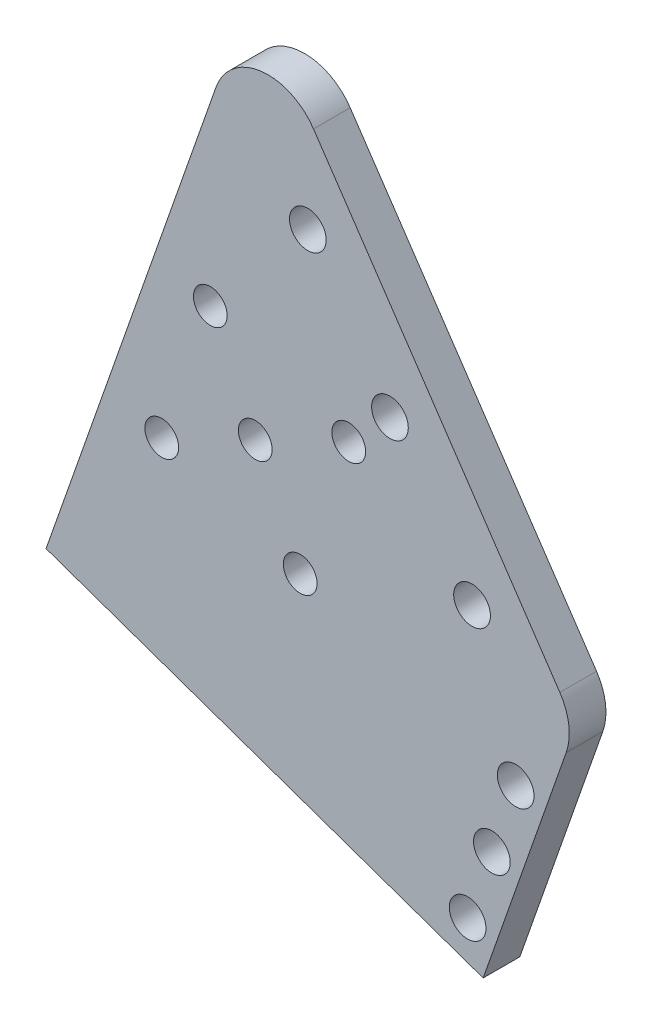
SolidWorks part; units mm, degrees
ref_plane "Front" through (0, 0, 0) normal (0, 0, 1) x (1, 0, 0)
ref_plane "Top" through (0, 0, 0) normal (0, 1, 0) x (1, 0, 0)
ref_plane "Right" through (0, 0, 0) normal (1, 0, 0) x (0, 0, -1)
sketch "Sketch1" plane through (0, 0, 0) normal (0, 0, 1) x (1, 0, 0)
  line L0 (-21.1234, 31.2849) -> (21.5169, -31.8676) construction
  line L1 (-13.2294, 36.615) -> (29.4109, -26.5376)
  line L11 (-30.1118, 34.437) -> (-59.5313, -49.454)
  line L12 (30.5052, -35.0197) -> (16.1374, -75.99)
  line L13 (16.1374, -75.99) -> (-59.5313, -49.454)
  line L14 (26.0532, -32.364) -> (13.445, -68.3167) construction
  arc A0 (-13.2294, 36.615) -> (-30.1118, 34.437) centre (-21.1234, 31.2849) ccw
  arc A1 (30.5052, -35.0197) -> (29.4109, -26.5376) centre (21.5169, -31.8676) ccw
  circle A2 centre (-14.2134, 21.0508) radius 3.175
  circle A3 centre (14.2134, -21.0508) radius 3.175
  circle A4 centre (0, 0) radius 3.175
  circle A5 centre (13.445, -68.3167) radius 3.175
  circle A6 centre (17.6478, -56.3323) radius 3.175
  circle A7 centre (21.7666, -44.3187) radius 3.175
  point P3 (0, 0)
  point P27 (0, 0)
  point P30 (26.0532, -32.364)
  point P31 (26.0532, -32.364)
  point P32 (26.0532, -32.364)
  point P33 (26.0532, -32.364)
  point P34 (0, 0)
  dimension "D2" = 6.35
  dimension "D3" = 25.4
  dimension "D4" = 25.4
  dimension "D5" = 9.525
  dimension "D6" = 63.1525
  dimension "D7" = 5.08
  dimension "D12" = 13.0515
  dimension "D14" = 6.35
  dimension "D15" = 12.7
  dimension "D9" = 6.35
  dimension "D16" = 12.7
  dimension "D8" = 80.1867
  dimension "D10" = 88.9
  dimension "D11" = 76.2
  dimension "D13" = 12.3485
extrude "Boss-Extrude2" add sketch "Sketch1" along normal blind 6.35
sketch "Sketch2" plane through (0, 0, 0) normal (0, 0, -1) x (-1, 0, 0)
  line L0 (59.5313, -49.454) -> (-16.1374, -75.99) construction
  line L1 (9.8871, -6.3013) -> (28.3431, 0.171)
  line L2 (8.0973, -10.0243) -> (14.5696, -28.4803)
  line L3 (18.2926, -30.2701) -> (36.7487, -23.7978)
  line L4 (32.0662, -1.6187) -> (38.5385, -20.0748)
  line L5 (7.1307, -7.2679) -> (39.5051, -22.8312) construction
  line L6 (15.5362, -31.2368) -> (31.0995, 1.1377) construction
  line L7 (30.1118, 34.437) -> (59.5313, -49.454) construction
  circle A0 centre (7.1307, -7.2679) radius 2.921
  circle A1 centre (31.0995, 1.1377) radius 2.921
  circle A2 centre (39.5051, -22.8312) radius 2.921
  circle A3 centre (15.5362, -31.2368) radius 2.921
  circle A4 centre (23.3179, -15.0495) radius 2.921
  point P0 (23.3179, -15.0495)
  dimension "D4" = 5.842
  dimension "D5" = 5.842
  dimension "D1" = 31.75
  dimension "D2" = 25.4
  dimension "D3" = 25.4
extrude "Cut-Extrude1" cut sketch "Sketch2" against normal through all contours A3 | A0 | A4 | A1 | A2 region at (-7.1307, -7.2679, 0) region at (-31.0995, 1.1377, 0) region at (-15.5362, -31.2368, 0) region at (-39.5051, -22.8312, 0) region at (-23.3179, -15.0495, 0)
